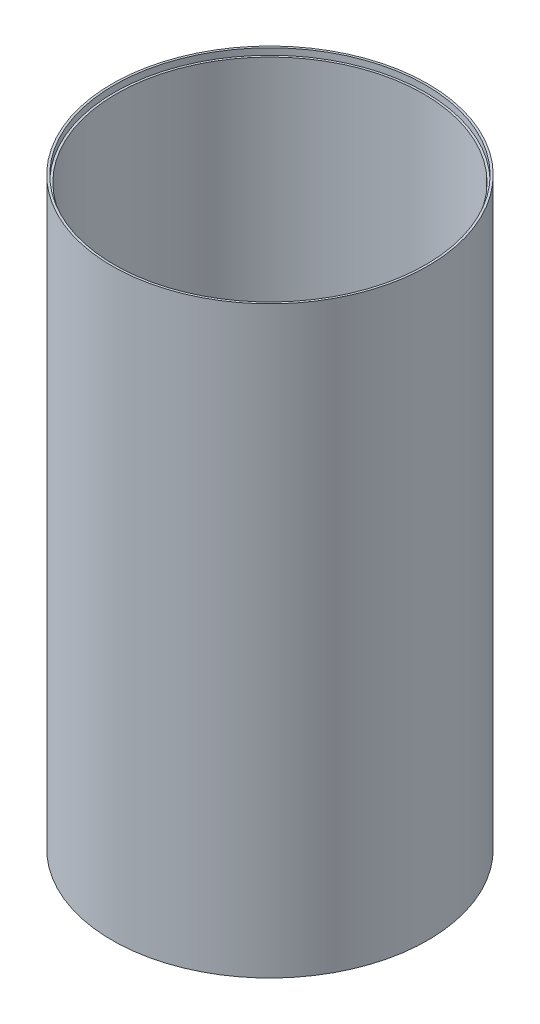
SolidWorks part; units mm, degrees
material "Polibutadiene (PB)"
ref_plane "Piano frontale" through (0, 0, 0) normal (0, 0, 1) x (1, 0, 0)
ref_plane "Piano superiore" through (0, 0, 0) normal (0, 1, 0) x (1, 0, 0)
ref_plane "Piano destro" through (0, 0, 0) normal (1, 0, 0) x (0, 0, -1)
sketch "Schizzo1" plane through (0, 0, 0) normal (0, 0, 1) x (1, 0, 0)
  line L0 (0, 0) -> (0, 21.1255) construction
  line L1 (-72, 0) -> (-72, 3)
  line L2 (-72, 3) -> (-71, 3)
  line L3 (-71, 3) -> (-71, 267)
  line L4 (-71, 267) -> (-72, 267)
  line L5 (-72, 267) -> (-72, 270)
  line L6 (-72, 270) -> (-73, 270)
  line L7 (-73, 270) -> (-73, 0)
  line L8 (-73, 0) -> (-72, 0)
  dimension "D1" = 2
  dimension "D2" = 142
  dimension "D3" = 3
  dimension "D4" = 270
  dimension "D5" = 3
revolve "Rivoluzione1" add sketch "Schizzo1" angle 360 about L0
